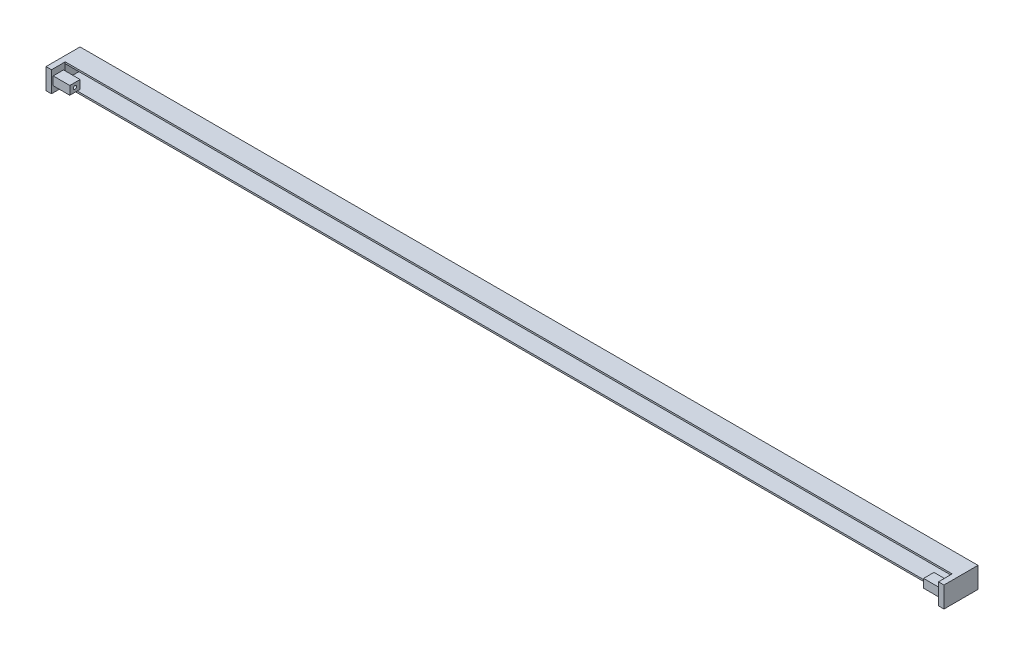
SolidWorks part; units mm, degrees
material "1060 Alloy"
ref_plane "Front Plane" through (0, 0, 0) normal (0, 0, 1) x (1, 0, 0)
ref_plane "Top Plane" through (0, 0, 0) normal (0, 1, 0) x (1, 0, 0)
ref_plane "Right Plane" through (0, 0, 0) normal (1, 0, 0) x (0, 0, -1)
sketch "Sketch1" plane through (0, 0, 0) normal (0, 0, 1) x (1, 0, 0)
  line L1 (0, 0) -> (1635, 0)
  line L2 (0, 0) -> (0, 38)
  line L3 (0, 38) -> (1635, 38)
  line L4 (1635, 0) -> (1635, 38)
  dimension "D1" = 38
  dimension "D2" = 1635
extrude "Boss-Extrude1" add sketch "Sketch1" along normal blind 62
sketch "Sketch2" plane through (0, 0, 62) normal (0, 0, 1) x (1, 0, 0)
  line L0 (1635, 38) -> (0, 38) construction
  line L1 (10, 38) -> (1625, 38)
  line L2 (10, 38) -> (10, 0)
  line L3 (10, 0) -> (1625, 0)
  line L4 (1625, 38) -> (1625, 0)
  line L5 (0, 0) -> (1635, 0) construction
  line L6 (1635, 0) -> (1635, 38) construction
  line L7 (0, 38) -> (0, 0) construction
  dimension "D1" = 10
  dimension "D2" = 10
extrude "Cut-Extrude1" cut sketch "Sketch2" against normal blind 25
sketch "Sketch3" plane through (10, 0, 0) normal (1, 0, 0) x (0, 0, -1)
  line L1 (-40.104, 26.745) -> (-58.9, 26.745)
  line L2 (-40.104, 26.745) -> (-40.104, 11.251)
  line L3 (-40.104, 11.251) -> (-58.9, 11.251)
  line L4 (-58.9, 26.745) -> (-58.9, 11.251)
  line L5 (-37, 38) -> (-62, 38) construction
  line L6 (-62, 38) -> (-62, 0) construction
  dimension "D1" = 18.796
  dimension "D2" = 15.494
  dimension "D3" = 11.255
  dimension "D4" = 3.1
extrude "Boss-Extrude2" add sketch "Sketch3" along normal blind 30.226
sketch "Sketch5" plane through (1625, 0, 0) normal (-1, 0, 0) x (0, 0, 1)
  line L0 (58.9, 26.74) -> (39.9812, 26.74)
  line L1 (58.9, 26.74) -> (58.9, 11.246)
  line L2 (58.9, 11.246) -> (39.9812, 11.246)
  line L3 (39.9812, 26.74) -> (39.9812, 11.246)
  line L4 (37, 38) -> (62, 38) construction
  line L5 (62, 0) -> (62, 38) construction
  dimension "D1" = 11.26
  dimension "D2" = 3.1
extrude "Boss-Extrude3" add sketch "Sketch5" along normal blind 30.226
sketch "Sketch6" plane through (40.226, 0, 0) normal (1, 0, 0) x (0, 0, -1)
  line L0 (-40.104, 11.251) -> (-40.104, 26.745) construction
  line L1 (-58.9, 26.745) -> (-58.9, 11.251) construction
  line L3 (-58.9, 11.251) -> (-40.104, 11.251) construction
  circle A0 centre (-49.504, 18.996) radius 3
  dimension "D1" = 9.4
  dimension "D2" = 9.396
  dimension "D3" = 7.745
extrude "Cut-Extrude2" cut sketch "Sketch6" against normal blind 10
sketch "Sketch7" plane through (1594.774, 0, 0) normal (-1, 0, 0) x (0, 0, 1)
  line L0 (58.9, 26.74) -> (39.9812, 26.74) construction
  line L1 (39.9812, 26.74) -> (39.9812, 11.246) construction
  circle A0 centre (49.3812, 18.995) radius 3
  dimension "D1" = 7.745
  dimension "D2" = 9.4
extrude "Cut-Extrude3" cut sketch "Sketch7" against normal blind 10
shell "Shell1" thickness 3 removed face at (817.5, 19, 37)
